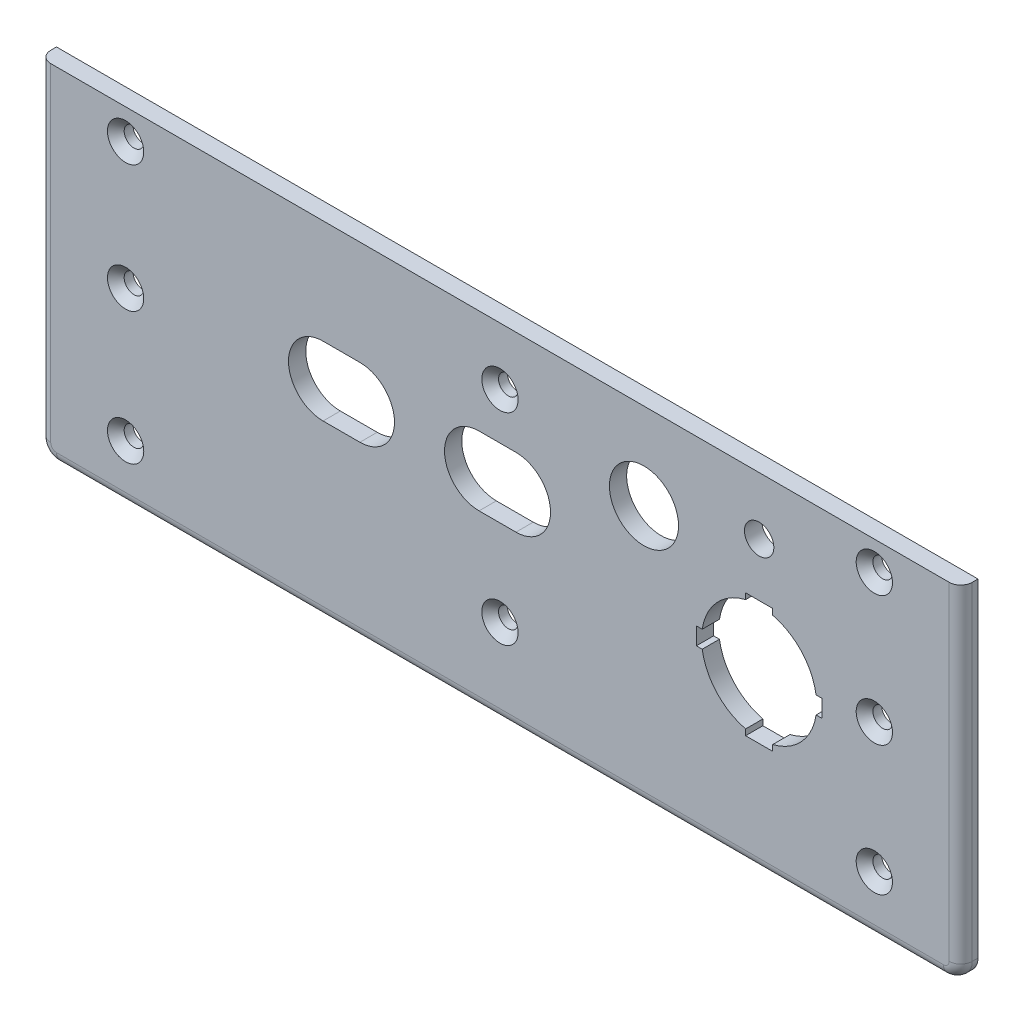
SolidWorks part; units mm, degrees
ref_plane "Front Plane" through (0, 0, 0) normal (0, 0, 1) x (1, 0, 0)
ref_plane "Top Plane" through (0, 0, 0) normal (0, 1, 0) x (1, 0, 0)
ref_plane "Right Plane" through (0, 0, 0) normal (1, 0, 0) x (0, 0, -1)
sketch "Sketch11" plane through (0, 0, 0) normal (0, 0, 1) x (1, 0, 0)
  line L0 (-44.8869, 31.5) -> (-45.8972, 31.5)
  line L1 (-45.8972, 31.5) -> (-45.8972, 28.5)
  line L2 (-45.8972, 28.5) -> (-44.8869, 28.5)
  line L3 (-35, 30) -> (-45.8972, 30) construction
  line L4 (-37.35, 20.28) -> (-37.35, 19.254)
  line L5 (-37.35, 19.254) -> (-32.65, 19.254)
  line L6 (-32.65, 19.254) -> (-32.65, 20.28)
  line L7 (-35, 30) -> (-35, 19.254) construction
  line L8 (-32.65, 40.746) -> (-32.65, 39.72)
  line L9 (-37.35, 40.746) -> (-32.65, 40.746)
  line L10 (-37.35, 39.72) -> (-37.35, 40.746)
  line L11 (-35, 18.7315) -> (-35, 30) construction
  line L12 (-25.1131, 31.5) -> (-24.1028, 31.5)
  line L13 (-24.1028, 31.5) -> (-24.1028, 28.5)
  line L14 (-24.1028, 28.5) -> (-25.1131, 28.5)
  line L15 (-35, 50) -> (-35, 30) construction
  line L17 (0, 0) -> (-160, 0)
  line L18 (0, 0) -> (0, 60)
  line L19 (0, 60) -> (-160, 60)
  line L20 (-160, 0) -> (-160, 60)
  line L21 (-83.6273, 35.9303) -> (-77.2273, 35.9303) construction
  line L22 (-83.6273, 41.9303) -> (-77.2273, 41.9303)
  line L23 (-83.6273, 29.9303) -> (-77.2273, 29.9303)
  line L24 (-110.7157, 35.9) -> (-104.3157, 35.9) construction
  line L25 (-110.7157, 41.9) -> (-104.3157, 41.9)
  line L26 (-110.7157, 29.9) -> (-104.3157, 29.9)
  arc A0 (-44.8869, 28.5) -> (-37.35, 20.28) centre (-35, 30) ccw
  circle A1 centre (-35, 30) radius 11 construction
  arc A2 (-32.65, 20.28) -> (-25.1131, 28.5) centre (-35, 30) ccw
  arc A3 (-37.35, 39.72) -> (-44.8869, 31.5) centre (-35, 30) ccw
  arc A4 (-25.1131, 31.5) -> (-32.65, 39.72) centre (-35, 30) ccw
  circle A5 centre (-35, 50) radius 2.55
  circle A6 centre (-55, 45) radius 6
  arc A7 (-103.7657, 35.9) -> (-104.3157, 36.45) centre (-104.3157, 35.9) ccw construction
  arc A8 (-110.7157, 36.45) -> (-111.2657, 35.9) centre (-110.7157, 35.9) ccw construction
  arc A9 (-76.6773, 35.9303) -> (-77.2273, 36.4803) centre (-77.2273, 35.9303) ccw construction
  arc A10 (-83.6273, 36.4803) -> (-84.1773, 35.9303) centre (-83.6273, 35.9303) ccw construction
  arc A11 (-103.7657, 35.9) -> (-104.3157, 36.45) centre (-104.3157, 35.9) ccw construction
  arc A12 (-110.7157, 36.45) -> (-111.2657, 35.9) centre (-110.7157, 35.9) ccw construction
  arc A13 (-76.6773, 35.9303) -> (-77.2273, 36.4803) centre (-77.2273, 35.9303) ccw construction
  arc A14 (-83.6273, 36.4803) -> (-84.1773, 35.9303) centre (-83.6273, 35.9303) ccw construction
  arc A15 (-83.6273, 41.9303) -> (-83.6273, 29.9303) centre (-83.6273, 35.9303) ccw
  arc A16 (-77.2273, 29.9303) -> (-77.2273, 41.9303) centre (-77.2273, 35.9303) ccw
  arc A17 (-110.7157, 41.9) -> (-110.7157, 29.9) centre (-110.7157, 35.9) ccw
  arc A18 (-104.3157, 29.9) -> (-104.3157, 41.9) centre (-104.3157, 35.9) ccw
  point P42 (-80.4273, 35.9303)
  point P47 (-107.5157, 35.9)
  dimension "D1" = 20
  dimension "D4" = 22
  dimension "D5" = 5.1
  dimension "D11" = 12
  dimension "D6" = 20
  dimension "D2" = 3
  dimension "D3" = 4.7
  dimension "D7" = 160
  dimension "D8" = 35
  dimension "D9" = 30
  dimension "D10" = 60
  dimension "D12" = 20
  dimension "D13" = 12
  dimension "D14" = 15
extrude "Boss-Extrude1" add sketch "Sketch11" along normal blind 3 contours L20 L17 L18 L19 A5 A4 L12 L13 L14 A2 L6 L5 L4 A0 L2 L1 L0 A3 L10 L9 L8
fillet "Fillet1" radius 2 3 edges at (-80, 0, 3) (-160, 30, 3) (0, 30, 3)
fillet "Fillet3" radius 3 4 edges at (-0.5858, 0.5858, 2.4142) (-159.4142, 0.5858, 2.4142) (-160, 0, 0.5) (0, 0, 0.5)
sketch "Sketch12" plane through (0, 0, 3) normal (0, 0, 1) x (1, 0, 0)
  line L1 (-80, 50) -> (-80, 60) construction
  line L2 (-2, 60) -> (-158, 60) construction
  circle A0 centre (-145, 9.7713) radius 3 construction
  circle A1 centre (-145, 32.7287) radius 3 construction
  circle A2 centre (-145, 54.7713) radius 3 construction
  circle A3 centre (-15, 10) radius 3 construction
  circle A4 centre (-15, 32.5) radius 3 construction
  circle A5 centre (-15, 55) radius 3 construction
  circle A6 centre (-145, 9.7713) radius 3
  circle A7 centre (-145, 32.7287) radius 3
  circle A8 centre (-145, 54.7713) radius 3
  circle A9 centre (-15, 10) radius 3
  circle A10 centre (-15, 32.5) radius 3
  circle A11 centre (-15, 55) radius 3
  circle A12 centre (-80, 50) radius 3
  circle A13 centre (-80, 15) radius 3
  circle A14 centre (-80, 50) radius 3 construction
  circle A15 centre (-80, 15) radius 3 construction
hole_wizard "CSK for M3 Flat Head Machine Screw1" positions "3DSketch1" profile "Sketch13" countersink size "M3" standard "ANSI Metric" end condition through all
sketch3d "3DSketch1"
  point P0 (-145, 54.7713, 3)
  point P3 (-145, 32.7287, 3)
  point P6 (-145, 9.7713, 3)
  point P9 (-15, 10, 3)
  point P12 (-15, 32.5, 3)
  point P15 (-15, 55, 3)
  point P18 (-80, 50, 3)
  point P21 (-80, 15, 3)
sketch "Sketch13" plane through (-145, 54.7713, 3) normal (1, 0, 0) x (0, -1, 0)
  line L0 (0, 0) -> (0, 3)
  line L1 (0, 3) -> (1.7, 3)
  line L2 (1.7, 3) -> (1.7, 1.45)
  line L3 (1.7, 1.45) -> (3.15, 0)
  line L5 (3.15, 0) -> (0, 0)
  line L6 (-1.7, 1.45) -> (-3.15, 0) construction
  line L11 (0, -6.35) -> (0, 107.95) construction
  dimension "Thru Hole Dia." = 3.4
  dimension "Thru Hole Depth" = 3
  dimension "Near C'Sink Dia." = 6.3
  dimension "Near C'Sink Angle" = 90
